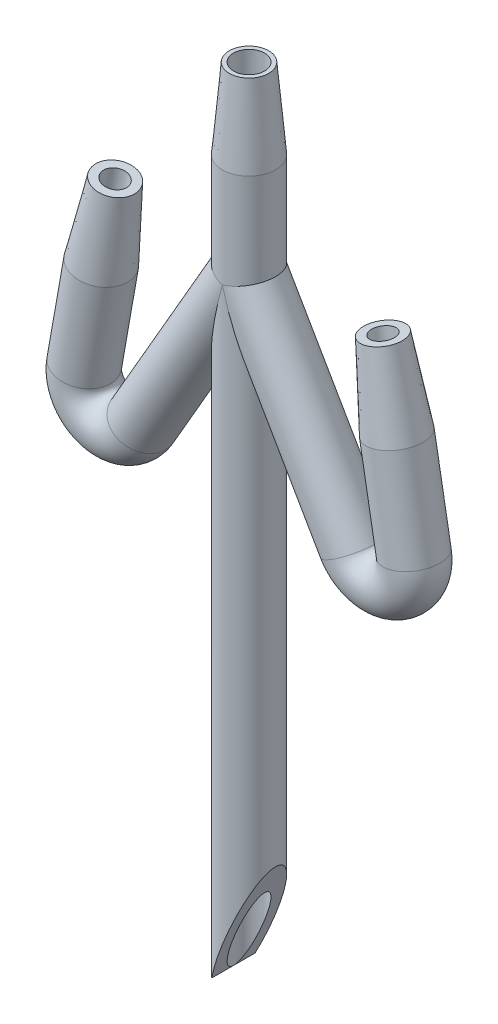
SolidWorks part; units mm, degrees
ref_plane "Front Plane" through (0, 0, 0) normal (0, 0, 1) x (1, 0, 0)
ref_plane "Top Plane" through (0, 0, 0) normal (0, 1, 0) x (1, 0, 0)
ref_plane "Right Plane" through (0, 0, 0) normal (1, 0, 0) x (0, 0, -1)
sketch "Sketch1" plane through (0, 0, 0) normal (0, 1, 0) x (1, 0, 0)
  circle A0 centre (0, 0) radius 1.75
  circle A1 centre (0, 0) radius 3
  dimension "D1" = 1.25
  dimension "D2" = 6
extrude "Boss-Extrude1" add sketch "Sketch1" along normal blind 88.9
sketch "Sketch2" plane through (0, 0, 0) normal (0, 0, 1) x (1, 0, 0)
  line L0 (-1.75, 0) -> (3, 12)
  line L1 (3.3, 0) -> (-3.3, 0) construction
  line L2 (3, 0) -> (3, 88.9) construction
  line L3 (3, 12) -> (3, 0)
  line L4 (3, 0) -> (-1.75, 0)
  line L5 (-1.75, 0) -> (-2.1668, -0.0217)
  dimension "D1" = 4.75
  dimension "D2" = 12
extrude "Cut-Extrude1" cut sketch "Sketch2" against normal through all and the other way through all contours L0 L3 L4
sketch "Sketch3" plane through (0, 0, 0) normal (0, 0, 1) x (1, 0, 0)
  line L0 (-16.5512, 63.5) -> (15.3182, 63.5) construction
  line L1 (3.3, 0) -> (-3.3, 0) construction
  line L2 (-3, 63.5) -> (-11.6525, 48.5134) construction
  line L3 (-3, 88.9) -> (-3, 0) construction
  dimension "D1" = 63.5
  dimension "D2" = 60
ref_plane "Plane1" through (-3, 63.5, 0) normal (-0.5, -0.866, 0) x (-0.866, 0.5, 0)
sketch "Sketch4" plane through (-3, 63.5, 0) normal (-0.5, -0.866, 0) x (-0.866, 0.5, 0)
  circle A0 centre (0, 0) radius 0.6
  dimension "D1" = 1.2
extrude "Cut-Extrude3" cut sketch "Sketch4" along normal blind 76.2 and the other way up to surface other way up to face at (0, 88.9, 1.75)
sketch "Sketch5" plane through (-3, 63.5, 0) normal (-0.5, -0.866, 0) x (-0.866, 0.5, 0)
  circle A0 centre (0, 0) radius 0.6
  circle A1 centre (0, 0) radius 3
  dimension "D1" = 6
  dimension "D2" = 1.2
ref_plane "Plane2" through (-7, 56.5718, 0) normal (-0.5, -0.866, 0) x (-0.866, 0.5, 0)
sketch "Sketch6" plane through (-7, 56.5718, 0) normal (-0.5, -0.866, 0) x (-0.866, 0.5, 0)
  circle A0 centre (0, 0) radius 0.6 construction
  circle A1 centre (0, 0) radius 3 construction
  circle A2 centre (0, 0) radius 0.6
  circle A3 centre (0, 0) radius 3
extrude "Boss-Extrude2" add sketch "Sketch6" along normal blind 10 and the other way up to surface other way up to face at (-2.9983, 64.6858, 0.1011)
mirror "Mirror2" about plane through (0, 0, 0) normal (1, 0, 0) of "Boss-Extrude2", "Cut-Extrude3"
sketch "Sketch7" plane through (0, 0, 0) normal (0, 0, 1) x (1, 0, 0)
  line L0 (-14.5981, 49.4115) -> (-9.4019, 46.4115) construction
  line L1 (-3, 63.5) -> (-11.6525, 48.5134) construction
  line L2 (-18.5393, 50.2917) -> (-15.0664, 69.9878)
  line L3 (3.3, 0) -> (-3.3, 0) construction
  arc A0 (-12, 47.9115) -> (-18.5393, 50.2917) centre (-15.0598, 49.6781) cw
  dimension "D1" = 20
  dimension "D2" = 80
sketch "Sketch8" plane through (17.7463, 30.7375, 0) normal (-0.5, -0.866, 0) x (0.866, -0.5, 0)
  circle A0 centre (-34.3481, 0) radius 0.6 construction
  circle A1 centre (-34.3481, 0) radius 3
  circle A2 centre (-34.3481, 0) radius 3
  circle A3 centre (-34.3481, 0) radius 0.6
  dimension "D1" = 0
sweep "Sweep1" add profiles "Sketch8" path "Sketch7"
mirror "Mirror3" about plane through (0, 0, 0) normal (1, 0, 0) of "Sweep1"
chamfer "Chamfer2" distance 20 angle 2 2 edges at (15.6572, 70.092, 0) (-15.6572, 70.092, 0)
chamfer "Chamfer1" distance 9 angle 5 3 edges at (0, 88.9, 3) (18.0208, 70.5088, 0) (-18.0208, 70.5088, 0)
ref_plane "Plane3" through (0, 15, 0) normal (0, 1, 0) x (1, 0, 0)
sketch "Sketch10" plane through (0, 15, 0) normal (0, 1, 0) x (1, 0, 0)
  circle A0 centre (0, 0) radius 3
  arc A1 (-1.75, -2.4367) -> (-1.75, 2.4367) centre (0, 0) ccw construction
  circle A2 centre (0, 0) radius 14.6267
